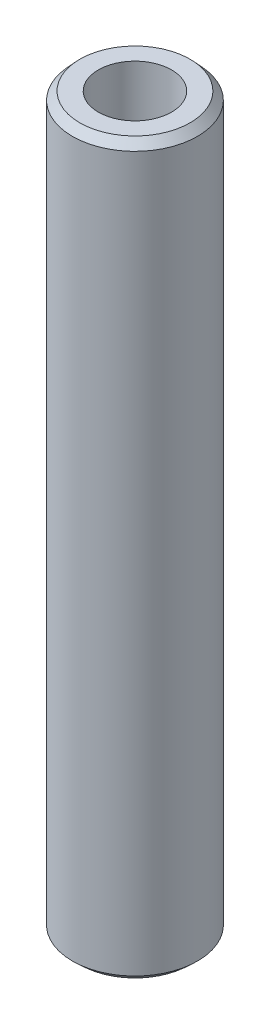
SolidWorks part; units mm, degrees
ref_plane "Front Plane" through (0, 0, 0) normal (0, 0, 1) x (1, 0, 0)
ref_plane "Top Plane" through (0, 0, 0) normal (0, 1, 0) x (1, 0, 0)
ref_plane "Right Plane" through (0, 0, 0) normal (1, 0, 0) x (0, 0, -1)
sketch "Sketch1" plane through (0, 0, 0) normal (0, 1, 0) x (1, 0, 0)
  circle A0 centre (0, 0) radius 37.5
  dimension "SHAFT_OD" = 75
extrude "Boss-Extrude1" add sketch "Sketch1" along normal blind 437.5616
sketch "Sketch2" plane through (0, 0, 0) normal (0, 1, 0) x (1, 0, 0)
  circle A0 centre (0, 0) radius 21.9629
  dimension "BORE_D" = 43.9258
extrude "Cut-Extrude1" cut sketch "Sketch2" along normal through all
chamfer "Chamfer1" distance 4.8285 angle 42.622 2 edges at (0, 437.5616, 37.5) (0, 0, 37.5) first distance on face at (0, 437.5616, 37.5) first distance on face at (0, 0, 21.9629)
